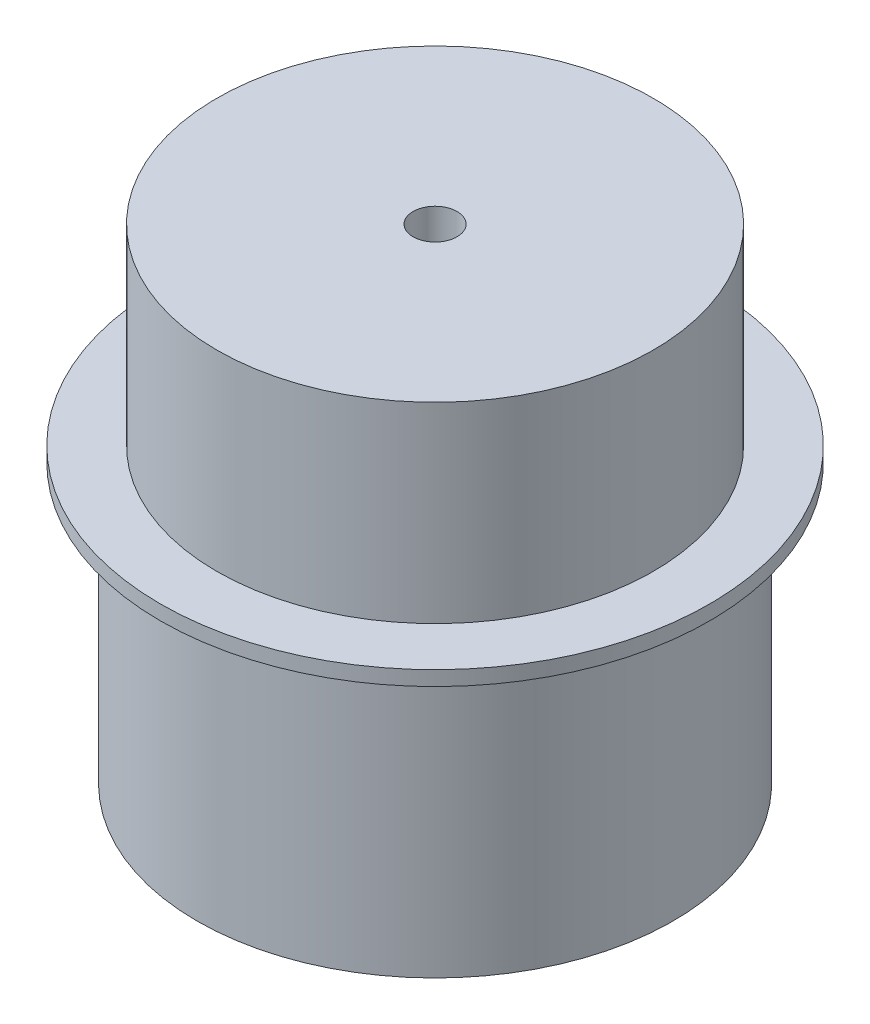
SolidWorks part; units mm, degrees
ref_plane "Спереди" through (0, 0, 0) normal (0, 0, 1) x (1, 0, 0)
ref_plane "Сверху" through (0, 0, 0) normal (0, 1, 0) x (1, 0, 0)
ref_plane "Справа" through (0, 0, 0) normal (1, 0, 0) x (0, 0, -1)
sketch "Эскиз1" plane through (0, 0, 0) normal (0, 0, 1) x (1, 0, 0)
  line L0 (0, 0) -> (0, 64.3029) construction
  line L37 (8.5163, 58.3357) -> (2, 62.0979) construction
  line L40 (30.5, 14.9146) -> (32.5, 14.9146)
  line L41 (32.5, 14.9146) -> (32.5, 52.9179)
  line L42 (8, 58.6338) -> (8.3476, 52.0019) construction
  line L43 (8.3476, 52.0019) -> (10.7476, 49.4019) construction
  line L44 (8, 58.6338) -> (8, 51.4355) construction
  line L45 (10.7476, 49.4019) -> (10.9672, 43.1119) construction
  line L46 (10.7476, 49.4019) -> (10.7476, 37.0019) construction
  line L50 (12.2182, 33.9946) -> (19.2771, 33.9946) construction
  line L51 (12.2182, 33.9946) -> (16.6302, 29.2146) construction
  line L53 (30.5, 14.9146) -> (30.5, 29.2146)
  line L55 (11.9976, 38.5019) -> (11.9976, 41.6565) construction
  line L56 (11.9976, 40.3132) -> (12.2182, 33.9946) construction
  line L57 (29.8, 62.0979) -> (29.8, 54.9179)
  line L59 (32.5, 52.9179) -> (37.5, 52.9179)
  line L60 (37.5, 52.9179) -> (37.5, 54.9179)
  line L61 (37.5, 54.9179) -> (29.8, 54.9179)
  line L63 (8.4851, 58.9311) -> (8.8784, 51.4269)
  line L65 (8.4993, 58.66) -> (8.8469, 52.0281) construction
  line L66 (8.8784, 51.4269) -> (11.1635, 48.9513)
  line L67 (11.1635, 48.9513) -> (11.3659, 43.156)
  line L68 (11.1473, 49.4159) -> (11.367, 43.1259) construction
  line L69 (12.4844, 40.6987) -> (12.7382, 33.4313)
  line L70 (12.4973, 40.3306) -> (12.7179, 34.0121) construction
  line L71 (12.7382, 33.4313) -> (16.6302, 29.2146) construction
  line L72 (16.9548, 29.2146) -> (30.5, 29.2146)
  line L73 (12.7382, 33.4313) -> (16.9548, 29.2146)
  line L74 (16.9548, 29.2146) -> (16.6302, 29.2146) construction
  line L75 (8.4851, 58.9311) -> (3, 62.0979)
  line L76 (8.7663, 58.7687) -> (2.25, 62.5309) construction
  line L77 (3, 62.0979) -> (29.8, 62.0979)
  arc A0 (11.9976, 40.3132) -> (10.9672, 43.1119) centre (11.33, 41.6565) ccw construction
  arc A2 (11.3659, 43.156) -> (12.4844, 40.6987) centre (11.33, 41.6565) cw
  point P8 (10.9083, 44.8)
  point P11 (11.33, 41.6565)
  point P15 (0, 61.8065)
  point P17 (11.9976, 38.5019)
  point P47 (4.6509, 61.4581)
  dimension "D5" = 16
  dimension "D14" = 3
  dimension "D7" = 61
  dimension "D3" = 2.6
  dimension "D4" = 3
  dimension "D6" = 60
  dimension "D8" = 4
  dimension "D9" = 2
  dimension "D10" = 2.4
  dimension "D11" = 2
  dimension "D12" = 20.15
  dimension "D13" = 11.33
  dimension "D15" = 1.25
  dimension "D16" = 10.9
  dimension "D17" = 4.78
  dimension "D18" = 2
  dimension "D19" = 14.3
  dimension "D20" = 29.8
  dimension "D21" = 9.18
  dimension "D22" = 5
  dimension "D23" = 2
  dimension "D24" = 0.5
  dimension "D25" = 0.4
  dimension "D26" = 6.29
  dimension "D27" = 0.5
  dimension "D28" = 0.5
revolve "Повернуть1" add sketch "Эскиз1" angle 360 about L0 reverse direction yes
sketch "Эскиз2" plane through (0, 62.0979, 0) normal (0, 1, 0) x (1, 0, 0)
  circle A0 centre (0, 0) radius 3 construction
  circle A1 centre (0, 0) radius 3
  circle A5 centre (0, 0) radius 29.8
extrude "Бобышка-Вытянуть1" add sketch "Эскиз2" along normal blind 19
